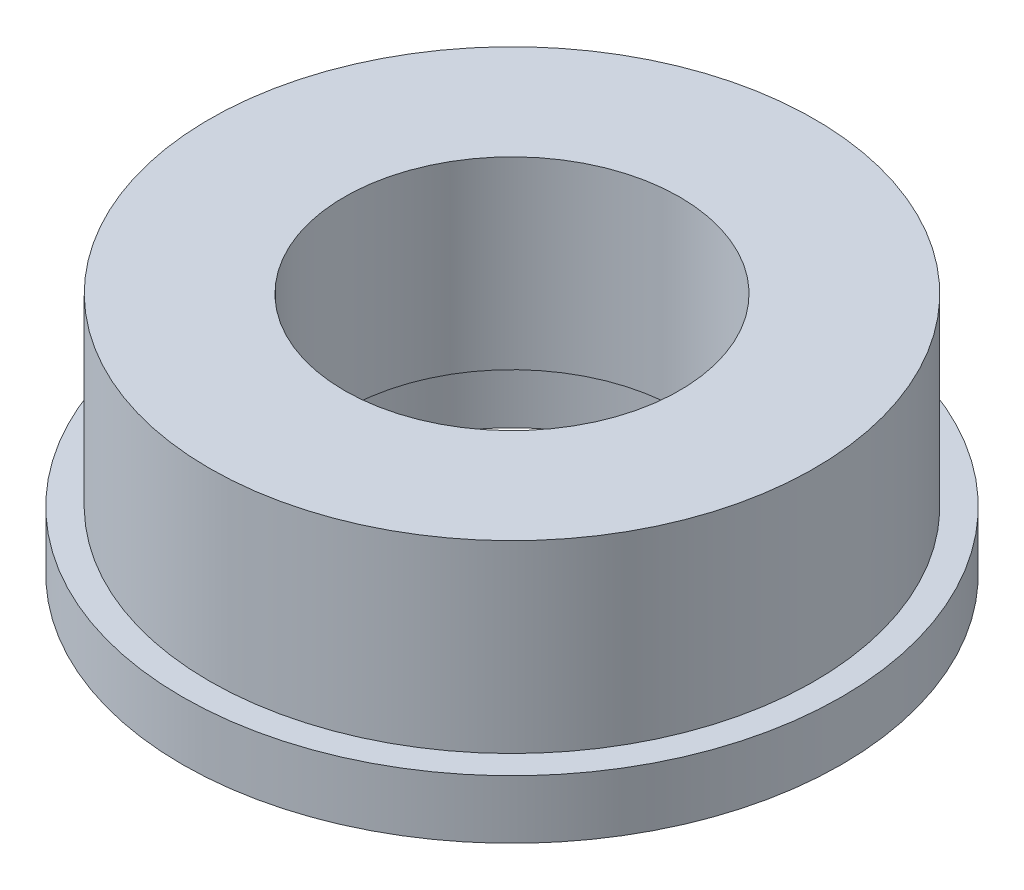
SolidWorks part; units mm, degrees
ref_plane "Front Plane" through (0, 0, 0) normal (1, 0, 0) x (0, 1, 0)
ref_plane "Top Plane" through (0, 0, 0) normal (0, 0, 1) x (0, 1, 0)
ref_plane "Right Plane" through (0, 0, 0) normal (0, 1, 0) x (-1, 0, 0)
sketch "Sketch2" plane through (0, 0, 0) normal (0, 0, 1) x (0, 1, 0)
  line L0 (-9.525, 53.66) -> (-9.525, 29.1925)
  line L1 (0, 53.66) -> (-9.525, 53.66)
  line L2 (0, 53.66) -> (0, 49.23)
  line L11 (0, 49.9725) -> (0, 10.4526) construction
  line L12 (0, 27.2875) -> (20, 27.2875)
  line L17 (30, 49.23) -> (30, 27.2875)
  line L18 (30, 49.23) -> (0, 49.23)
  line L19 (562.356, 26.9875) -> (0, 26.9875) construction
  line L22 (-9.525, 29.1925) -> (0, 29.1925)
  line L23 (0, 29.1925) -> (0, 53.66)
  line L24 (0, 27.2875) -> (0, 29.1925)
  line L25 (-9.525, 28.8925) -> (-9.525, -28.8925) construction
  line L26 (-9.525, 28.8925) -> (-9.525, -28.8925)
  line L27 (30, 27.2875) -> (20, 27.2875)
  dimension "D1" = 30
  dimension "D2" = 53.66
  dimension "D3" = 0.3
  dimension "D4" = 0.3
  dimension "D5" = 49.23
ref_axis "Axis1" through (0, 52.9763, 0) along (0, -1, 0)
revolve "Revolve1" add sketch "Sketch2" angle 360 about axis through (0, 52.9763, 0) along (0, -1, 0) region at (-41.4262, -4.7625, 0) region at (-38.2588, 15, 0)
